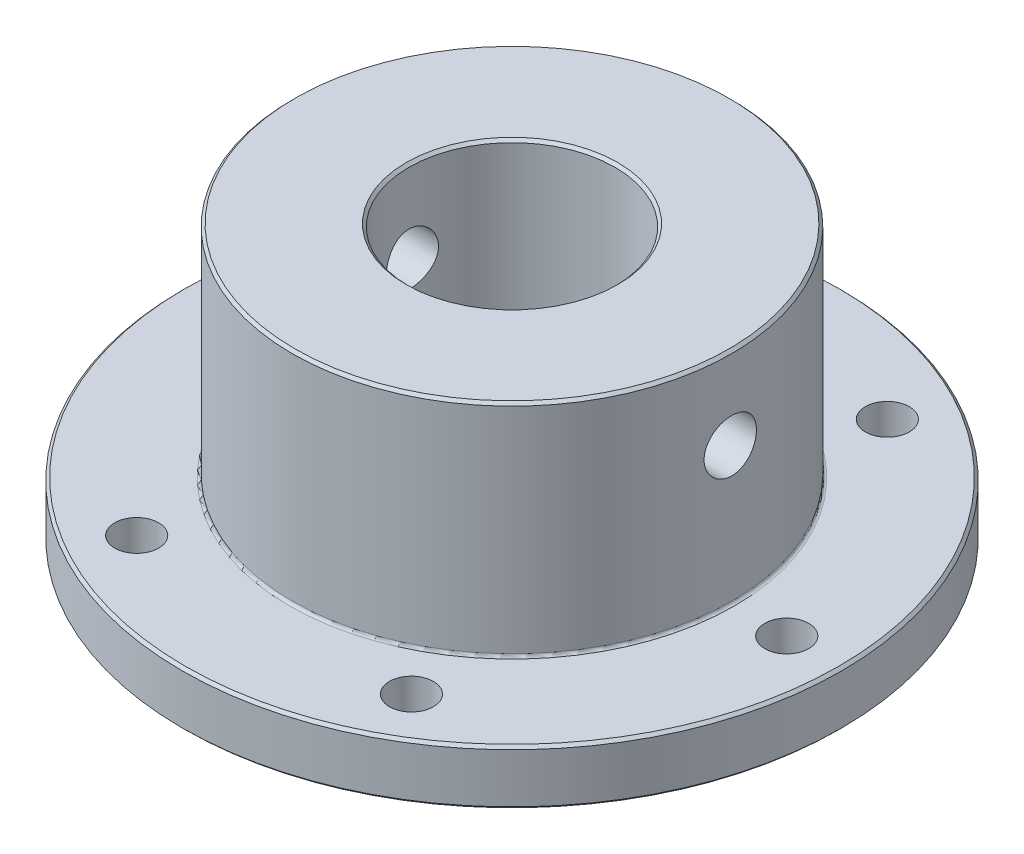
SolidWorks part; units mm, degrees
material "AISI 1020"
ref_plane "Alzado" through (0, 0, 0) normal (0, 0, 1) x (1, 0, 0)
ref_plane "Planta" through (0, 0, 0) normal (0, 1, 0) x (1, 0, 0)
ref_plane "Vista lateral" through (0, 0, 0) normal (1, 0, 0) x (0, 0, -1)
sketch "Croquis1" plane through (0, 0, 0) normal (0, 1, 0) x (1, 0, 0)
  line L0 (0, 0) -> (25, -43.3013) construction
  line L1 (50, 0) -> (25, 43.3013) construction
  line L2 (25, 43.3013) -> (-25, 43.3013) construction
  line L3 (-25, 43.3013) -> (-50, 0) construction
  line L4 (-50, 0) -> (-25, -43.3013) construction
  line L5 (-25, -43.3013) -> (25, -43.3013) construction
  line L6 (25, -43.3013) -> (50, 0) construction
  circle A0 centre (0, 0) radius 18.75
  circle A1 centre (0, 0) radius 60
  circle A2 centre (0, 0) radius 43.3013 construction
  circle A3 centre (25, -43.3013) radius 4
  circle A4 centre (-25, -43.3013) radius 4
  circle A5 centre (-50, 0) radius 4
  circle A6 centre (-25, 43.3013) radius 4
  circle A7 centre (25, 43.3013) radius 4
  circle A8 centre (50, 0) radius 4
  dimension "D1" = 37.5
  dimension "D5" = 8
  dimension "D6" = 120
  dimension "D2" = 50
  dimension "D4" = 50
  dimension "D3" = 6
extrude "Saliente-Extruir1" add sketch "Croquis1" along normal blind 10
sketch "Croquis2" plane through (0, 10, 0) normal (0, 1, 0) x (1, 0, 0)
  circle A0 centre (0, 0) radius 18.75
  circle A1 centre (0, 0) radius 40
  dimension "D1" = 37.5
  dimension "D2" = 80
extrude "Saliente-Extruir2" add sketch "Croquis2" along normal blind 40
chamfer "Chaflán2" distance 0.5 angle 45 4 edges at (0, 10, 60) (0, 0, 60) (0, 50, 40) (0, 50, 18.75)
fillet "Redondeo1" radius 0.5 1 edges at (0, 10, 40)
sketch "Croquis3" plane through (0, 0, 0) normal (1, 0, 0) x (0, 0, -1)
  line L0 (0, 50) -> (0, 10) construction
  line L1 (19.25, 50) -> (-19.25, 50) construction
  line L2 (59.5, 10) -> (-59.5, 10) construction
  line L3 (39.5, 50) -> (-39.5, 50) construction
  circle A0 centre (0, 35) radius 4.7625
  dimension "D1" = 9.525
  dimension "D2" = 40
  dimension "D3" = 15
  dimension "D4" = 35
extrude "Cortar-Extruir1" cut sketch "Croquis3" against normal through all and the other way through all
